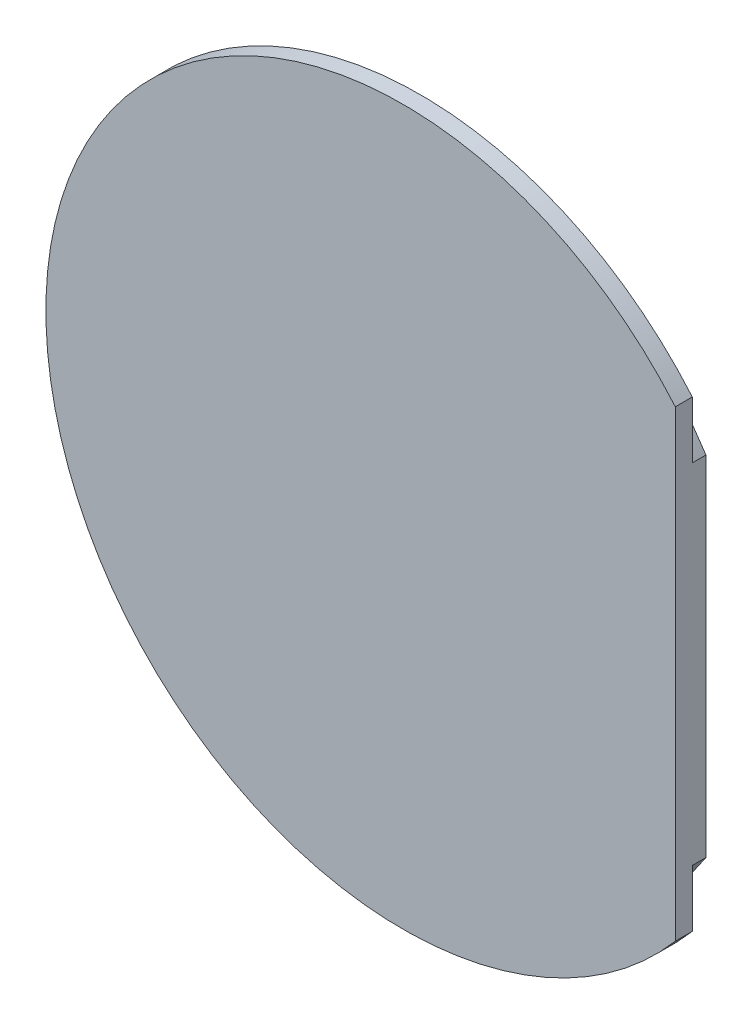
SolidWorks part; units mm, degrees
ref_plane "Front Plane" through (0, 0, 0) normal (0, 0, 1) x (1, 0, 0)
ref_plane "Top Plane" through (0, 0, 0) normal (0, 1, 0) x (1, 0, 0)
ref_plane "Right Plane" through (0, 0, 0) normal (1, 0, 0) x (0, 0, -1)
sketch "Sketch1" plane through (0, 0, 0) normal (0, 0, 1) x (1, 0, 0)
  circle A0 centre (0, 0) radius 21
extrude "Boss-Extrude1" add sketch "Sketch1" along normal blind 1 from offset 27 offset against normal yes
sketch "Sketch2" plane through (0, 0, 0) normal (0, 0, 1) x (1, 0, 0)
  circle A0 centre (0, 0) radius 19
extrude "Boss-Extrude2" add sketch "Sketch2" along normal blind 0.8 from offset 27.8 offset against normal yes
sketch "Sketch3" plane through (0, 0, 0) normal (0, 0, 1) x (1, 0, 0)
  line L0 (16, -30) -> (30, -30)
  line L1 (30, -30) -> (30, 30)
  line L2 (30, 30) -> (16, 30)
  line L3 (16, 30) -> (16, -30)
extrude "Cut-Extrude1" cut sketch "Sketch3" against normal through all and the other way through all
